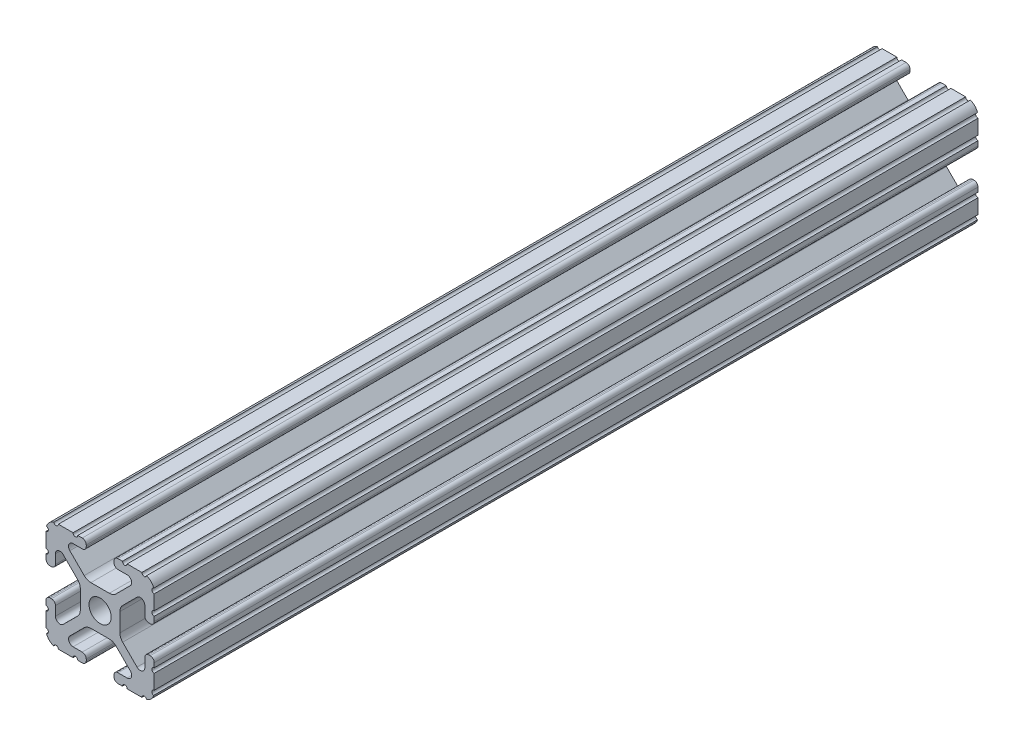
SolidWorks part; units mm, degrees
ref_plane "Front Plane" through (0, 0, 0) normal (0, 0, 1) x (1, 0, 0)
ref_plane "Top Plane" through (0, 0, 0) normal (0, 1, 0) x (1, 0, 0)
ref_plane "Right Plane" through (0, 0, 0) normal (1, 0, 0) x (0, 0, -1)
sketch "Sketch2" plane through (0, 0, 0) normal (0, 0, 1) x (1, 0, 0)
  line L0 (0, 12.7) -> (0, -12.7) construction
  line L1 (-12.7, 0) -> (12.7, 0) construction
  line L2 (3.2512, -12.7) -> (12.7, -12.7)
  line L3 (12.7, -12.7) -> (12.7, -3.2512)
  line L4 (3.2512, -12.7) -> (3.2512, -10.4902)
  line L5 (3.2512, -10.4902) -> (8.9276, -10.4902)
  line L6 (8.9276, -10.4902) -> (3.0856, -4.6482)
  line L7 (0, 0) -> (12.7, -12.7) construction
  line L8 (12.7, -3.2512) -> (10.4902, -3.2512)
  line L9 (10.4902, -3.2512) -> (10.4902, -8.9276)
  line L10 (10.4902, -8.9276) -> (4.6482, -3.0856)
  circle A0 centre (0, 0) radius 2.6035
  arc A1 (6.3485, -10.4902) -> (7.1039, -8.6665) centre (6.3485, -9.4219) ccw construction
  point P8 (0, -4.6482)
  dimension "Center Hole Diameter" = 5.207
  dimension "Rail Height" = 25.4
  dimension "Rail Width" = 25.4
  dimension "T-Slot Width" = 6.5024
  dimension "Slot Inner Width" = 14.8336
  dimension "Thickness" = 2.2098
  dimension "Slot Depth" = 5.842
  dimension "D1" = 2.2098
sketch "Sketch3" plane through (0, 0, 0) normal (1, 0, 0) x (0, 0, -1)
  line L0 (-96.6796, -12.7) -> (96.6796, -12.7) construction
  line L1 (-71.2796, 0) -> (71.2796, 0) construction
  line L2 (96.6796, 0) -> (-96.6796, 0) construction
sketch "Sketch4" plane through (0, 0, 0) normal (0, 0, 1) x (1, 0, 0)
  line L0 (4.1904, -12.7) -> (10.1173, -12.7)
  line L1 (3.2512, -12.7) -> (12.7, -12.7) construction
  line L2 (3.2512, -12.7) -> (3.2512, -10.4902) construction
  line L3 (3.2512, -10.4902) -> (8.9276, -10.4902) construction
  line L4 (3.2512, -11.4294) -> (3.2512, -11.7608)
  line L5 (4.1904, -10.4902) -> (6.3485, -10.4902)
  line L6 (0, -4.6482) -> (2.164, -4.6482)
  line L7 (8.9276, -10.4902) -> (3.0856, -4.6482) construction
  line L8 (3.7373, -5.2999) -> (7.1039, -8.6665)
  line L9 (12.7, -12.7) -> (12.7, -3.2512) construction
  line L10 (10.4902, -8.9276) -> (4.6482, -3.0856) construction
  line L11 (10.4902, -3.2512) -> (10.4902, -8.9276) construction
  line L12 (10.4902, -6.3485) -> (10.4902, -4.1904)
  line L13 (12.7, -3.2512) -> (10.4902, -3.2512) construction
  line L14 (11.4294, -3.2512) -> (11.7608, -3.2512)
  line L15 (12.7, -4.1904) -> (12.7, -10.1173)
  line L16 (8.6665, -7.1039) -> (5.2999, -3.7373)
  line L17 (4.6482, 0) -> (4.6482, -2.164)
  line L18 (-12.7, 0) -> (12.7, 0) construction
  line L19 (0, -4.6482) -> (0, -2.6035)
  line L20 (0, 12.7) -> (0, -12.7) construction
  line L21 (4.6482, 0) -> (2.6035, 0)
  arc A0 (3.2512, -11.7608) -> (4.1904, -12.7) centre (4.1904, -11.7608) ccw
  arc A2 (3.2512, -11.4294) -> (4.1904, -10.4902) centre (4.1904, -11.4294) cw
  arc A3 (6.3485, -10.4902) -> (7.1039, -8.6665) centre (6.3485, -9.4219) ccw
  arc A4 (2.164, -4.6482) -> (3.7373, -5.2999) centre (2.164, -6.8732) cw
  arc A5 (10.1173, -12.7) -> (12.7, -10.1173) centre (10.1173, -10.1173) ccw
  arc A6 (8.6665, -7.1039) -> (10.4902, -6.3485) centre (9.4219, -6.3485) ccw
  arc A7 (10.4902, -4.1904) -> (11.4294, -3.2512) centre (11.4294, -4.1904) cw
  arc A8 (11.7608, -3.2512) -> (12.7, -4.1904) centre (11.7608, -4.1904) cw
  arc A9 (5.2999, -3.7373) -> (4.6482, -2.164) centre (6.8732, -2.164) cw
  circle A10 centre (0, 0) radius 2.6035 construction
  arc A11 (0, -2.6035) -> (2.6035, 0) centre (0, 0) ccw
  dimension "D1" = 2.5827
  dimension "D2" = 2.225
  dimension "D3" = 0.9392
extrude "Boss-Extrude1" add sketch "Sketch4" along normal up to vertex (96.6796 mm away) from vertex up to point (0, -12.7, 96.6796) starting at point (0, -12.7, -96.6796)
sketch "Sketch5" plane through (0, 0, 0) normal (0, 0, 1) x (1, 0, 0)
  line L0 (3.2512, -12.7) -> (12.7, -12.7) construction
  line L1 (4.1904, -10.4902) -> (6.3485, -10.4902) construction
  line L3 (0, 0) -> (12.7, -12.7) construction
  line L4 (6.3485, -10.4902) -> (6.3485, -12.7) construction
  line L5 (8.9276, -10.4902) -> (3.0856, -4.6482) construction
  circle A0 centre (10.3562, -12.7) radius 0.5524
  circle A1 centre (5.796, -12.7) radius 0.5524
  circle A2 centre (12.7, -10.3562) radius 0.5524
  circle A3 centre (12.7, -5.796) radius 0.5524
  point P10 (5.2694, -10.4902)
  point P12 (9.4219, -6.3485)
  dimension "D1" = 1.1049
extrude "Cut-Extrude1" cut sketch "Sketch5" against normal through all both and the other way through all
mirror "Mirror1" about plane through (0, 0, 0) normal (1, 0, 0) of bodies 137 134
mirror "Mirror2" about plane through (0, 0, 0) normal (0, 1, 0) of bodies 135
equation "\"D1@Sketch2\"=\"Thickness@Sketch2\""
equation "\"D2@Sketch4\"=\"Slot Inner Width@Sketch2\"*0.15"
equation "\"D1@Sketch4\"=\"D3@Sketch4\"*2.75"
equation "\"D3@Sketch4\"=\"Thickness@Sketch2\"*0.425"
equation "\"D1@Sketch5\"=\"Thickness@Sketch2\"*0.5"
equation "\"D1@Boss-Extrude1\"=\"Length@Sketch3\""
